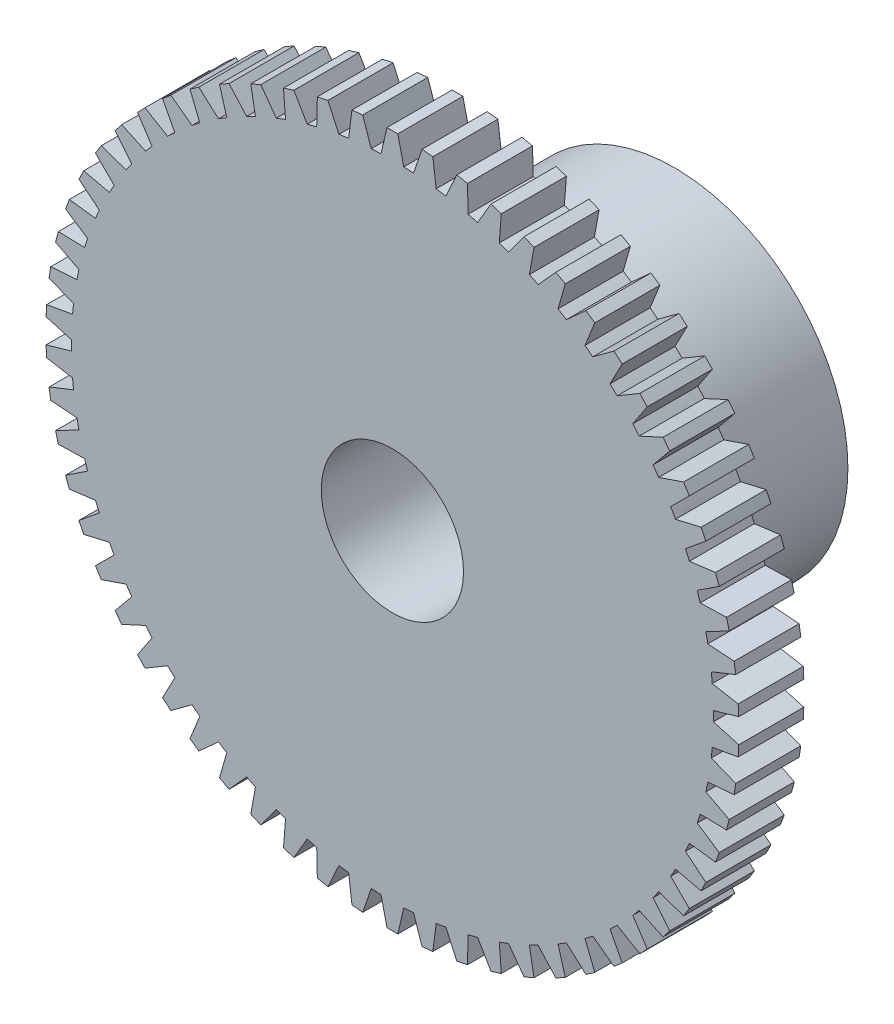
SolidWorks part; units mm, degrees
ref_plane "Front Plane" through (0, 0, 0) normal (0, 0, 1) x (1, 0, 0)
ref_plane "Top Plane" through (0, 0, 0) normal (0, 1, 0) x (1, 0, 0)
ref_plane "Right Plane" through (0, 0, 0) normal (1, 0, 0) x (0, 0, -1)
sketch "Sketch1" plane through (0, 0, 0) normal (0, 0, 1) x (1, 0, 0)
  circle A0 centre (0, 0) radius 14.8
  dimension "D1" = 29.6
extrude "Boss-Extrude1" add sketch "Sketch1" along normal blind 3
sketch "Sketch2" plane through (0, 0, 3) normal (0, 0, 1) x (1, 0, 0)
  line L0 (0, 17.802) -> (0, 0) construction
  line L3 (0.25, 15.9737) -> (-0.25, 15.9737)
  line L12 (-0.25, 15.9737) -> (-0.55, 14.6758)
  line L13 (-0.55, 14.6758) -> (0.5499, 14.6758)
  line L15 (0.25, 15.9737) -> (0.5499, 14.6758)
  point P3 (0, 15.9737)
  dimension "D1" = 0.25
  dimension "D2" = 166.985
  dimension "D3" = 15.9737
  dimension "D4" = 166.99
  dimension "D5" = 0.25
  dimension "D6" = 14.6758
extrude "Boss-Extrude2" add sketch "Sketch2" against normal blind 3
pattern_circular "CirPattern1" count 62 over 360 about axis through (0, 0, 3) along (0, 0, -1) of "Boss-Extrude2"
sketch "Sketch3" plane through (0, 0, 3) normal (0, 0, 1) x (1, 0, 0)
  circle A0 centre (0, 0) radius 8
extrude "Boss-Extrude3" add sketch "Sketch3" against normal blind 13
sketch "Sketch5" plane through (0, 0, 3) normal (0, 0, 1) x (1, 0, 0)
  circle A0 centre (0, 0) radius 3.278
extrude "Cut-Extrude2" cut sketch "Sketch5" against normal blind 13
